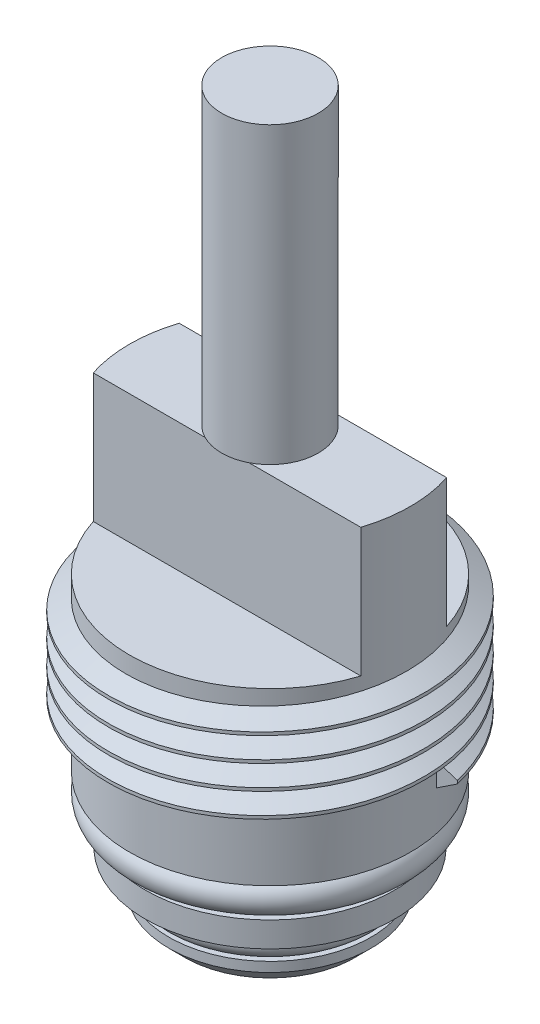
SolidWorks part; units mm, degrees
material "Brass"
ref_plane "Front Plane" through (0, 0, 0) normal (0, 0, 1) x (1, 0, 0)
ref_plane "Top Plane" through (0, 0, 0) normal (0, 1, 0) x (1, 0, 0)
ref_plane "Right Plane" through (0, 0, 0) normal (1, 0, 0) x (0, 0, -1)
sketch "Sketch1" plane through (0, 0, 0) normal (0, 0, 1) x (1, 0, 0)
  line L0 (0, -6751.5455) -> (0, 330825.7272) construction
  line L1 (2.825, -7.1274) -> (-2.825, -7.1274) construction
  line L2 (1.5, 13.7964) -> (-1.5, 13.7964)
  line L3 (1.5, 13.7964) -> (1.5, 4.6524)
  line L4 (1.5, 4.6524) -> (-1.5, 4.6524)
  line L5 (-1.5, 13.7964) -> (-1.5, 4.6524)
  line L6 (1.5, 13.7964) -> (-1.5, 4.6524) construction
  line L7 (1.5, 4.6524) -> (-1.5, 13.7964) construction
  line L8 (3.14, -7.5524) -> (-3.14, -7.5524)
  line L9 (3.14, -7.5524) -> (3.14, -8.3524)
  line L10 (3.14, -8.3524) -> (-3.14, -8.3524)
  line L11 (-3.14, -7.5524) -> (-3.14, -8.3524)
  line L12 (3.14, -7.5524) -> (-3.14, -8.3524) construction
  line L13 (3.14, -8.3524) -> (-3.14, -7.5524) construction
  line L14 (3.87, -5.9224) -> (-3.87, -5.9224)
  line L15 (3.87, -5.9224) -> (3.87, -6.7024)
  line L16 (3.87, -6.7024) -> (-3.87, -6.7024)
  line L17 (-3.87, -5.9224) -> (-3.87, -6.7024)
  line L18 (3.87, -5.9224) -> (-3.87, -6.7024) construction
  line L19 (3.87, -6.7024) -> (-3.87, -5.9224) construction
  line L20 (3.32, -4.6524) -> (-3.32, -4.6524)
  line L21 (3.32, -4.6524) -> (3.32, -5.9224)
  line L22 (3.32, -5.9224) -> (-3.32, -5.9224)
  line L23 (-3.32, -4.6524) -> (-3.32, -5.9224)
  line L24 (3.32, -4.6524) -> (-3.32, -5.9224) construction
  line L25 (3.32, -5.9224) -> (-3.32, -4.6524) construction
  line L26 (4.365, 4.6524) -> (-4.365, 4.6524)
  line L27 (4.365, 4.6524) -> (4.365, -4.6524)
  line L28 (4.365, -4.6524) -> (-4.365, -4.6524)
  line L29 (-4.365, 4.6524) -> (-4.365, -4.6524)
  line L30 (4.365, 4.6524) -> (-4.365, -4.6524) construction
  line L31 (4.365, -4.6524) -> (-4.365, 4.6524) construction
  line L32 (0, 13.7964) -> (0, -8.3524)
  circle A0 centre (-2.825, -7.1274) radius 0.425
  circle A1 centre (2.825, -7.1274) radius 0.425
  circle A2 centre (-3.8425, -5.1749) radius 0.5225
  circle A3 centre (3.8425, -5.1749) radius 0.5225
  point P1 (0, 9.2244)
  point P8 (0, -6.3124)
  point P9 (0, -7.9524)
  point P18 (0, -5.2874)
  point P23 (0, 0)
  point P35 (0, -7.1274)
  dimension "D12" = 6.5
  dimension "D2" = 8.73
  dimension "D3" = 6.28
  dimension "D4" = 0.8
  dimension "D5" = 0.85
  dimension "D6" = 7.74
  dimension "D7" = 0.78
  dimension "D8" = 6.64
  dimension "D9" = 1.27
  dimension "D10" = 3
  dimension "D11" = 9.144
  dimension "D13" = 22.1488
revolve "Revolve2" add sketch "Sketch1" angle 360 about L32 region at (-0.75, 9.2244, 0) region at (-2.1825, 0, 0) region at (-1.66, -5.2874, 0) region at (-1.935, -6.3124, 0) region at (-1.57, -7.9524, 0)
revolve "Revolve3" add sketch "Sketch1<5>" angle 360 about L32 region at (-3.8425, -5.1749, 0) region at (-2.825, -7.1274, 0)
sketch "Sketch1<5>" plane through (0, 0, 0) normal (0, 0, 1) x (1, 0, 0) same geometry as "Sketch1"
sketch "Sketch2" plane through (0, 4.6524, 0) normal (0, 1, 0) x (1, 0, 0)
  line L0 (0, 4.365) -> (0, -4.365) construction
  line L1 (0, 1.335) -> (0, -1.335) construction
  line L2 (4.365, 4.365) -> (-4.365, 4.365)
  line L3 (4.365, 4.365) -> (4.365, 1.335)
  line L4 (4.365, 1.335) -> (-4.365, 1.335)
  line L5 (-4.365, 4.365) -> (-4.365, 1.335)
  line L6 (4.365, 4.365) -> (-4.365, 1.335) construction
  line L7 (4.365, 1.335) -> (-4.365, 4.365) construction
  line L8 (4.365, -1.335) -> (-4.365, -1.335)
  line L9 (4.365, -1.335) -> (4.365, -4.365)
  line L10 (4.365, -4.365) -> (-4.365, -4.365)
  line L11 (-4.365, -1.335) -> (-4.365, -4.365)
  line L12 (4.365, -1.335) -> (-4.365, -4.365) construction
  line L13 (4.365, -4.365) -> (-4.365, -1.335) construction
  circle A0 centre (0, 0) radius 4.365 construction
  point P5 (0, 2.85)
  point P10 (0, -2.85)
  point P18 (0, 0)
  dimension "D1" = 2.67
extrude "Cut-Extrude1" cut sketch "Sketch2" against normal blind 4
thread "Thread1" pitch 1 method extrude profile "Thread Profile1" start angle 0, offset 0, length 3.35, pitch 0.75, diameter 8.73
ref_plane "Plane1" through (-4.365, 0.6524, 0) normal (0, 0, 1) x (-1, 0, 0)
sketch "Thread Profile1" plane through (-4.365, 0.6524, 0) normal (0, 0, 1) x (-1, 0, 0)
  line L0 (0, 0) -> (0, 1) construction
  line L1 (0, 0) -> (0.5413, 0.3125)
  line L2 (0.5413, 0.3125) -> (0.5413, 0.4125)
  line L3 (0.5413, 0.4125) -> (0, 0.725)
  line L4 (0.5413, 0.3625) -> (0, 0.3625) construction
  line L11 (0, 0) -> (0, 0.725)
  point P2 (0, 0)
  dimension "Pitch" = 1
  dimension "Profile_Angle" = 60
  dimension "Profile_Land" = 0.1
  dimension "Profile_Height" = 0.5413
chamfer "Chamfer1" distance 0.5 1 edges at (-3.14, -8.3524, 0)
ref_plane "max_compression" through (0, 10.7824, 0) normal (0, 1, 0) x (1, 0, 0)
